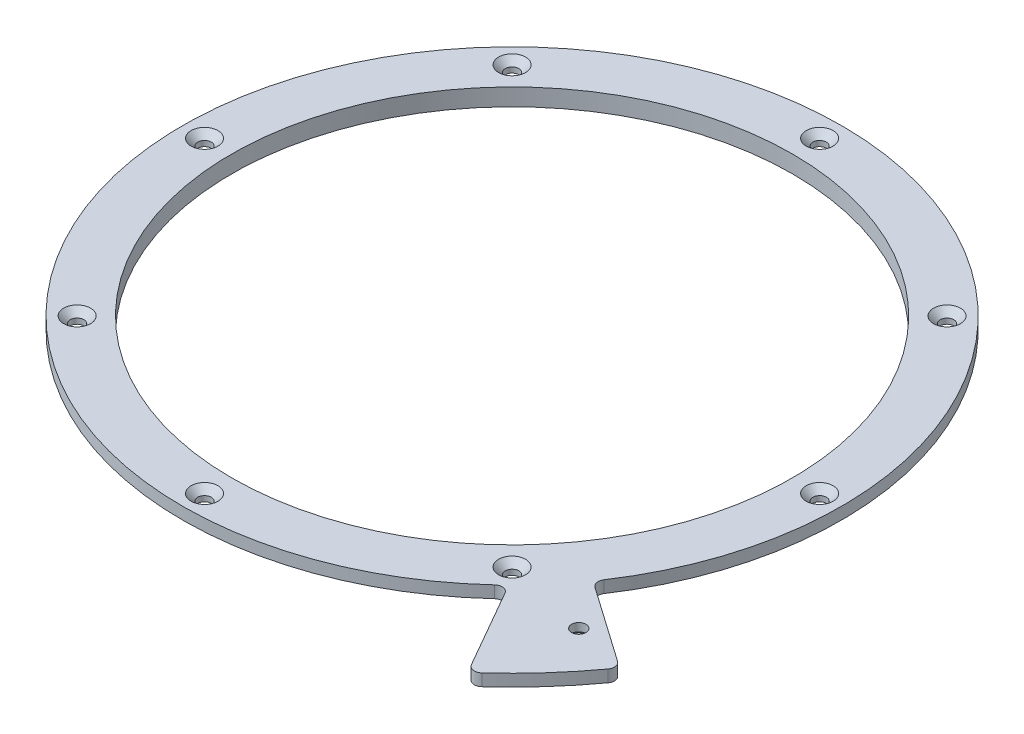
SolidWorks part; units mm, degrees
ref_plane "Plano frontal" through (0, 0, 0) normal (0, 0, 1) x (1, 0, 0)
ref_plane "Plano superior" through (0, 0, 0) normal (0, 1, 0) x (1, 0, 0)
ref_plane "Plano direito" through (0, 0, 0) normal (1, 0, 0) x (0, 0, -1)
sketch "Esboço1" plane through (0, 0, 0) normal (0, 1, 0) x (1, 0, 0)
  circle A0 centre (0, 0) radius 70
  circle A1 centre (0, 0) radius 82.26
  dimension "D1" = 140
  dimension "D2" = 164.52
extrude "Ressalto-extrusão1" add sketch "Esboço1" along normal blind 3
sketch "Esboço2" plane through (0, 0, 0) normal (0, -1, 0) x (1, 0, 0)
  circle A0 centre (0, 0) radius 73
  circle A1 centre (0, 0) radius 70
  circle A2 centre (0, 0) radius 70 construction
  dimension "D1" = 146
extrude "Ressalto-extrusão2" add sketch "Esboço2" along normal blind 1.3
sketch "Esboço3" plane through (0, 3, 0) normal (0, 1, 0) x (1, 0, 0)
  circle A0 centre (0, 0) radius 76.76 construction
  circle A2 centre (-76.76, 0) radius 1.5
  circle A3 centre (-54.2775, 54.2775) radius 1.5
  circle A4 centre (0, 76.76) radius 1.5
  circle A5 centre (54.2775, 54.2775) radius 1.5
  circle A6 centre (76.76, 0) radius 1.5
  circle A7 centre (54.2775, -54.2775) radius 1.5
  circle A8 centre (0, -76.76) radius 1.5
  circle A9 centre (-54.2775, -54.2775) radius 1.5
  circle A10 centre (0, 0) radius 70 construction
  point P5 (-76.76, 0)
  point P10 (-54.2775, 54.2775)
  point P12 (0, 76.76)
  point P14 (54.2775, 54.2775)
  point P16 (76.76, 0)
  point P18 (54.2775, -54.2775)
  point P20 (0, -76.76)
  point P22 (-54.2775, -54.2775)
  point P24 (0, 0)
  dimension "D1" = 6.76
  dimension "D2" = 3
  dimension "D3" = 8
hole_wizard "Escareado para parafuso Allen sextavado escareado de M31" positions "Esboço3" profile "Esboço4" countersink size "M3" standard "ISO" end condition up to next
sketch "Esboço4" plane through (0, 3, 0) normal (1, 0, 0) x (0, 0, 1)
  line L0 (0, 0) -> (0, 3)
  line L1 (0, 3) -> (1.7, 3)
  line L2 (1.7, 3) -> (1.7, 1.66)
  line L3 (1.7, 1.66) -> (3.36, 0)
  line L5 (3.36, 0) -> (0, 0)
  line L6 (-1.7, 1.66) -> (-3.36, 0) construction
  line L11 (0, -6.35) -> (0, 107.95) construction
  dimension "Thru Hole Dia." = 3.4
  dimension "Thru Hole Depth" = 3
  dimension "Near C'Sink Dia." = 6.72
  dimension "Near C'Sink Angle" = 90
sketch "Esboço5" plane through (0, 3, 0) normal (0, 1, 0) x (1, 0, 0)
  line L0 (0, 0) -> (0, -82.26) construction
  line L1 (0, 0) -> (58.1666, -58.1666) construction
  line L5 (67.3834, -47.1824) -> (0, 0) construction
  line L6 (59.6287, -61.8363) -> (71.5112, -82.5771)
  line L8 (89.4822, -62.6561) -> (67.3834, -47.1824)
  line L9 (59.6287, -61.8363) -> (57.7585, -58.5719)
  circle A0 centre (0, 0) radius 82.26 construction
  arc A3 (71.5112, -82.5771) -> (89.4822, -62.6561) centre (0, 0) ccw
  arc A4 (57.7585, -58.5719) -> (67.3834, -47.1824) centre (0, 0) ccw
  arc A5 (60.3018, -55.95) -> (17.7673, -80.3183) centre (0, 0) ccw construction
  point P10 (0, 0)
  dimension "D2" = 10
  dimension "D1" = 45
extrude "Ressalto-extrusão3" add sketch "Esboço5" against normal up to surface (3 mm away) up to face at (-76.76, 0, 1.7)
fillet "Filete1" radius 2 4 edges at (57.7585, 1.5, 58.5719) (67.3834, 1.5, 47.1824) (89.4822, 1.5, 62.6561) (71.5112, 1.5, 82.5771)
sketch "Esboço8" plane through (0, 3, 0) normal (0, 1, 0) x (1, 0, 0)
  line L0 (59.0289, -60.7893) -> (70.2894, -80.4444)
  line L1 (69.0023, -48.3159) -> (87.8286, -61.4982)
  line L2 (59.0289, -60.7893) -> (57.7585, -58.5719)
  line L3 (69.0023, -48.3159) -> (67.3834, -47.1824)
  circle A1 centre (0, 0) radius 82.26 construction
  arc A2 (68.4844, -45.5697) -> (55.9336, -60.317) centre (0, 0) ccw construction
  dimension "D1" = 25.191
  dimension "D2" = 14.9118
sketch "Esboço9" plane through (0, 3, 0) normal (0, 1, 0) x (1, 0, 0)
  circle A0 centre (75.867, -59.2265) radius 1.8
  circle A1 centre (75.867, -59.2265) radius 1.8 construction
extrude "Corte-extrusão3" cut sketch "Esboço9" against normal through all
chamfer "Chanfro2" distance 1 angle 45 1 edges at (75.867, 0, 61.0265)
